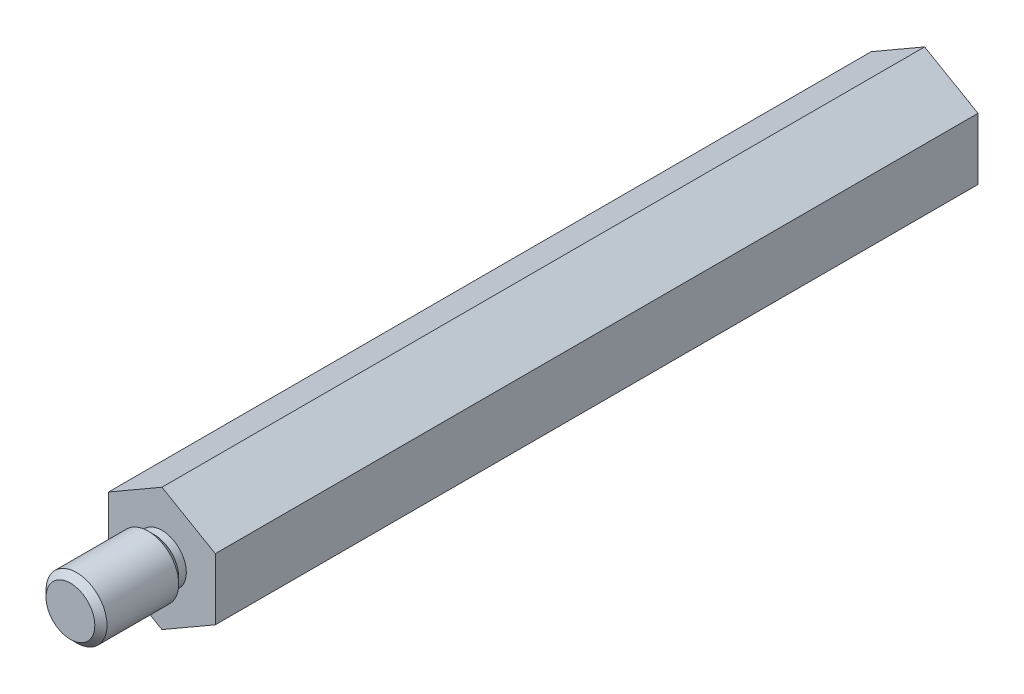
SolidWorks part; units mm, degrees
ref_plane "Спереди" through (0, 0, 0) normal (0, 0, 1) x (1, 0, 0)
ref_plane "Сверху" through (0, 0, 0) normal (0, 1, 0) x (1, 0, 0)
ref_plane "Справа" through (0, 0, 0) normal (1, 0, 0) x (0, 0, -1)
sketch "Эскиз1" plane through (0, 0, 0) normal (0, 0, 1) x (1, 0, 0)
  line L1 (0, 4.0415) -> (-3.5, 2.0207)
  line L2 (-3.5, 2.0207) -> (-3.5, -2.0207)
  line L3 (-3.5, -2.0207) -> (0, -4.0415)
  line L4 (0, -4.0415) -> (3.5, -2.0207)
  line L5 (3.5, -2.0207) -> (3.5, 2.0207)
  line L6 (3.5, 2.0207) -> (0, 4.0415)
  circle A0 centre (0, 0) radius 3.5 construction
  dimension "D1" = 7
extrude "Вытянуть1" add sketch "Эскиз1" along normal blind 50
sketch "Эскиз2" plane through (0, 0, 50) normal (0, 0, 1) x (1, 0, 0)
  circle A0 centre (0, 0) radius 2
  dimension "D1" = 4
extrude "Вытянуть2" add sketch "Эскиз2" along normal blind 6
sketch "Эскиз3" plane through (0, 0, 50) normal (0, 0, 1) x (1, 0, 0)
  circle A0 centre (0, 0) radius 1.6
  circle A1 centre (0, 0) radius 2 construction
  circle A2 centre (0, 0) radius 2
  dimension "D1" = 3.2
extrude "Вырез-Вытянуть3" cut sketch "Эскиз3" along normal blind 0.5
chamfer "Фаска1" distance 0.4 angle 45 2 edges at (2, 0, 50.5) (2, 0, 56)
hole_wizard "Отверстие с зазором M31" positions "Трехмерный эскиз2" profile "Эскиз5" hole size "M3" standard "Ansi Метрический"
sketch3d "Трехмерный эскиз2"
  point P0 (0, 0, 0)
  point P2 (0, 0, 0)
  point P3 (0, 0, 0)
sketch "Эскиз5" plane through (0, 0, 0) normal (1, 0, 0) x (0, 1, 0)
  line L0 (0, 0) -> (0, 8.6609)
  line L1 (0, 8.6609) -> (1.1, 8)
  line L2 (1.1, 8) -> (1.1, 0.4)
  line L3 (1.1, 0.4) -> (1.5, 0)
  line L5 (1.5, 0) -> (0, 0)
  line L6 (-1.1, 0.4) -> (-1.5, 0) construction
  line L10 (0, 8.6609) -> (-1.1, 8) construction
  line L11 (0, -6.35) -> (0, 107.95) construction
  dimension "Диаметр отверстия" = 2.2
  dimension "Глубина отверстия" = 8
  dimension "Диаметр передней зенковки" = 3
  dimension "Угол передней зенковки" = 90
  dimension "Угол заточки сверла" = 118
